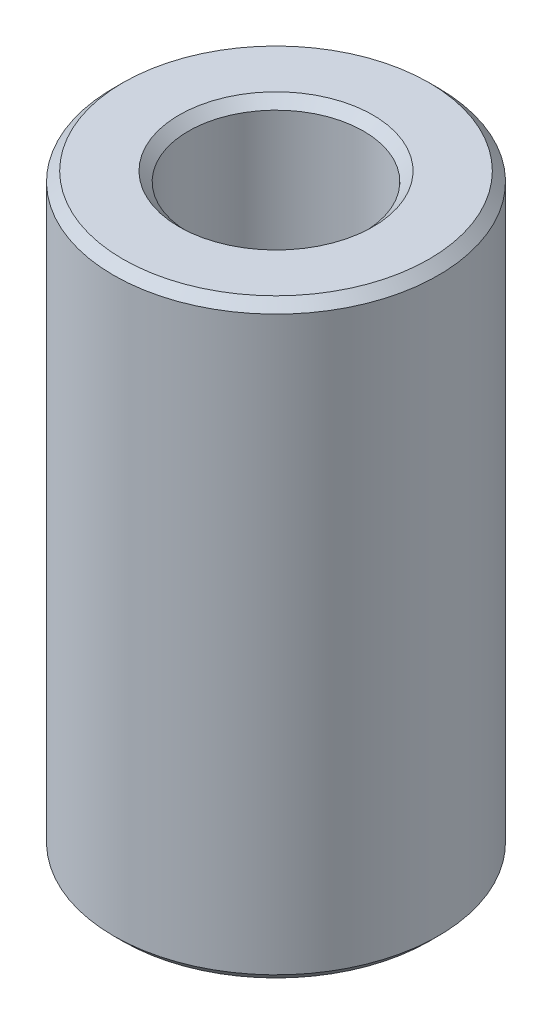
SolidWorks part; units mm, degrees
ref_plane "Front Plane" through (0, 0, 0) normal (0, 0, 1) x (1, 0, 0)
ref_plane "Top Plane" through (0, 0, 0) normal (0, 1, 0) x (1, 0, 0)
ref_plane "Right Plane" through (0, 0, 0) normal (1, 0, 0) x (0, 0, -1)
sketch "Sketch1" plane through (0, 0, 0) normal (0, 1, 0) x (1, 0, 0)
  circle A0 centre (0, 0) radius 15
  dimension "SLEEVE_OD" = 30
extrude "Boss-Extrude1" add sketch "Sketch1" along normal blind 54.6031
sketch "Sketch2" plane through (0, 0, 0) normal (0, 1, 0) x (1, 0, 0)
  circle A0 centre (0, 0) radius 8.0971
  dimension "BORE_D" = 16.1941
extrude "Cut-Extrude1" cut sketch "Sketch2" along normal through all
chamfer "Chamfer1" distance 0.8602 angle 45 4 edges at (0, 54.6031, 8.0971) (0, 0, 8.0971) (0, 0, 15) (0, 54.6031, 15)
